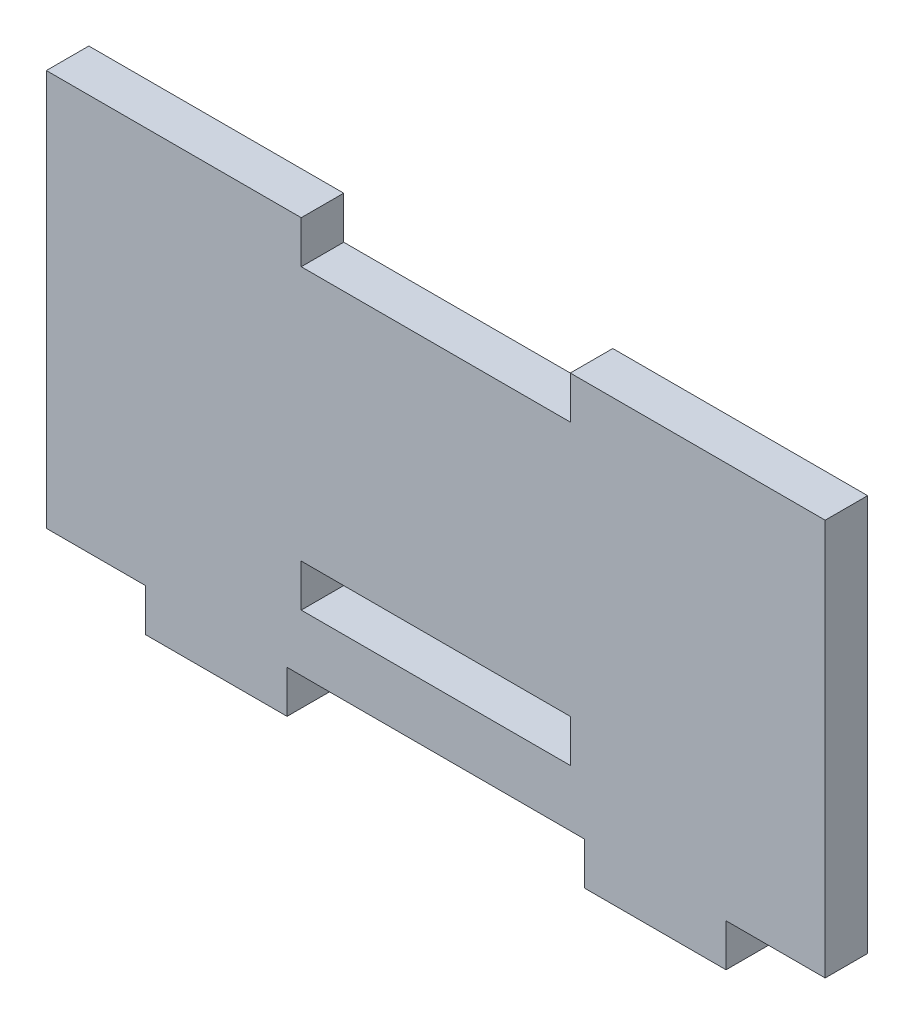
SolidWorks part; units mm, degrees
ref_plane "Front Plane" through (0, 0, 0) normal (0, 0, 1) x (1, 0, 0)
ref_plane "Top Plane" through (0, 0, 0) normal (0, 1, 0) x (1, 0, 0)
ref_plane "Right Plane" through (0, 0, 0) normal (1, 0, 0) x (0, 0, -1)
sketch "Sketch1" plane through (0, 0, 0) normal (0, 0, 1) x (1, 0, 0)
  line L0 (0, 0) -> (0, 28)
  line L1 (0, 28) -> (18, 28)
  line L2 (18, 28) -> (18, 25)
  line L3 (18, 25) -> (37, 25)
  line L4 (37, 25) -> (37, 28)
  line L5 (37, 28) -> (55, 28)
  line L6 (55, 28) -> (55, 0)
  line L7 (0, 0) -> (7, 0)
  line L8 (27.5, 25) -> (27.5, 7) construction
  line L9 (38, 0) -> (31, 0)
  line L11 (7, 0) -> (7, -3)
  line L12 (7, -3) -> (17, -3)
  line L13 (17, -3) -> (17, 0)
  line L14 (17, 0) -> (24, 0)
  line L15 (38, -3) -> (38, 0)
  line L16 (48, -3) -> (38, -3)
  line L17 (48, 0) -> (48, -3)
  line L19 (55, 0) -> (48, 0)
  line L21 (37, 7) -> (37, 4)
  line L22 (37, 7) -> (18, 7)
  line L23 (27.5, 7) -> (27.5, 4)
  line L24 (37, 4) -> (18, 4)
  line L25 (18, 7) -> (18, 4)
  line L26 (24, 0) -> (31, 0)
  dimension "D1" = 28
  dimension "D2" = 18
  dimension "D3" = 19
  dimension "D4" = 18
  dimension "D5" = 3
  dimension "D6" = 3
  dimension "D7" = 3
  dimension "D8" = 7
  dimension "D9" = 10
  dimension "D10" = 7
  dimension "D11" = 3
  dimension "D13" = 3
  dimension "D15" = 9.5
  dimension "D16" = 3
extrude "Boss-Extrude1" add sketch "Sketch1" along normal blind 3 contours L9 L15 L16 L17 L19 L6 L5 L4 L3 L22 L21 L24 L25 L2 L1 L0 L7 L11 L12 L13 L14 region at (27.5, 13.2207, 0)
